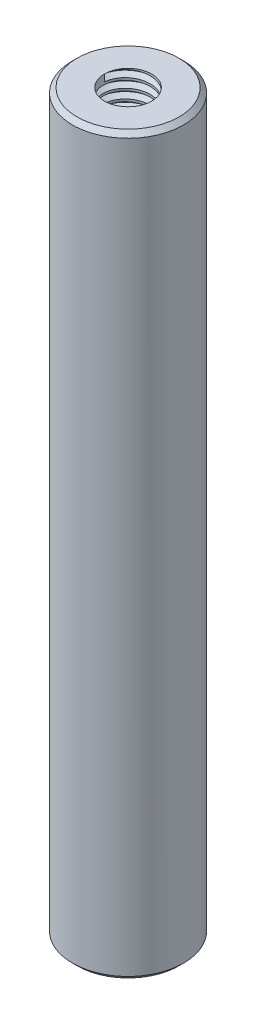
SolidWorks part; units mm, degrees
material "6061-T6 (SS)"
ref_plane "Alzado" through (0, 0, 0) normal (0, 0, 1) x (1, 0, 0)
ref_plane "Planta" through (0, 0, 0) normal (0, 1, 0) x (1, 0, 0)
ref_plane "Vista lateral" through (0, 0, 0) normal (1, 0, 0) x (0, 0, -1)
sketch "Croquis2" plane through (0, 0, 0) normal (0, 1, 0) x (1, 0, 0)
  circle A0 centre (0, 0) radius 4.7625
  dimension "D1" = 9.525
extrude "Saliente-Extruir1" add sketch "Croquis2" along normal mid plane 62.992
chamfer "Chaflán1" distance 0.3969 angle 45 2 edges at (0, -31.496, 4.7625) (0, 31.496, 4.7625)
sketch "Croquis3" plane through (0, 0, 0) normal (0, 1, 0) x (1, 0, 0)
  circle A0 centre (0, 0) radius 2.0193
  dimension "D1" = 4.0386
extrude "Tap Hole 1" cut sketch "Croquis3" against normal blind 19.05 from surface starting at face at (0, 31.496, 4.3656)
extrude "Tap Hole 2" cut sketch "Croquis3<2>" along normal blind 19.05 from surface starting at face at (0, -31.496, 4.3656)
sketch "Croquis3<2>" plane through (0, 0, 0) normal (0, 1, 0) x (1, 0, 0) same geometry as "Croquis3"
sketch "Croquis4" plane through (0, 0, 0) normal (0, 1, 0) x (1, 0, 0)
  circle A0 centre (0, 0) radius 2.4892
  dimension "D1" = 4.9784
extrude "Clearance Hole" [suppressed] cut sketch "Croquis4" against normal through all both and the other way through all
thread "Rosca1" pitch 0.7937 method cut profile "Perfil de rosca1" start angle 0, offset 0, length 0, pitch 0.7937, diameter 4.0386
ref_plane "Plano1" through (-2.0193, 31.496, 0) normal (0, 0, 1) x (-1, 0, 0)
sketch "Perfil de rosca1" plane through (-2.0193, 31.496, 0) normal (0, 0, 1) x (-1, 0, 0)
  line L0 (0, 0) -> (0, 0.7937) construction
  line L1 (0, 0) -> (0.4296, 0.248)
  line L2 (0.4296, 0.248) -> (0.4296, 0.3473)
  line L3 (0.4296, 0.3473) -> (0, 0.5953)
  line L4 (0.4296, 0.2977) -> (0, 0.2977) construction
  line L11 (0, 0) -> (0, 0.5953)
  point P2 (0, 0)
  dimension "Pitch" = 0.7937
  dimension "Profile_Angle" = 60
  dimension "Profile_Land" = 0.0992
  dimension "Profile_Height" = 0.4296
thread "Rosca2" pitch 0.7937 method cut profile "Perfil de rosca2" start angle 0, offset 0, length 0, pitch 0.7937, diameter 4.0386
ref_plane "Plano2" through (2.0193, -31.496, 0) normal (0, 0, 1) x (1, 0, 0)
sketch "Perfil de rosca2" plane through (2.0193, -31.496, 0) normal (0, 0, 1) x (1, 0, 0)
  line L0 (0, 0) -> (0, 0.7937) construction
  line L1 (0, 0) -> (0.4296, 0.248)
  line L2 (0.4296, 0.248) -> (0.4296, 0.3473)
  line L3 (0.4296, 0.3473) -> (0, 0.5953)
  line L4 (0.4296, 0.2977) -> (0, 0.2977) construction
  line L11 (0, 0) -> (0, 0.5953)
  point P2 (0, 0)
  dimension "Pitch" = 0.7937
  dimension "Profile_Angle" = 60
  dimension "Profile_Land" = 0.0992
  dimension "Profile_Height" = 0.4296
equation "\"OD\"= 0.375pulgadas"
equation "\"Largo\"= 2.48"
equation "\"Tap Hole\"= IIF ( \"OD\" = 0.375pulgadas , 0.1590pulgadas , 0.201pulgadas )"
equation "\"Spacer Hole\"= IIF ( \"OD\" = 0.375pulgadas , 0.196pulgadas , 0.257pulgadas )"
equation "\"D1@Croquis2\"=\"OD\""
equation "\"D1@Saliente-Extruir1\"=\"Largo\""
equation "\"D1@Croquis3\"=\"Tap Hole\""
equation "\"D1@Croquis4\"=\"Spacer Hole\""
